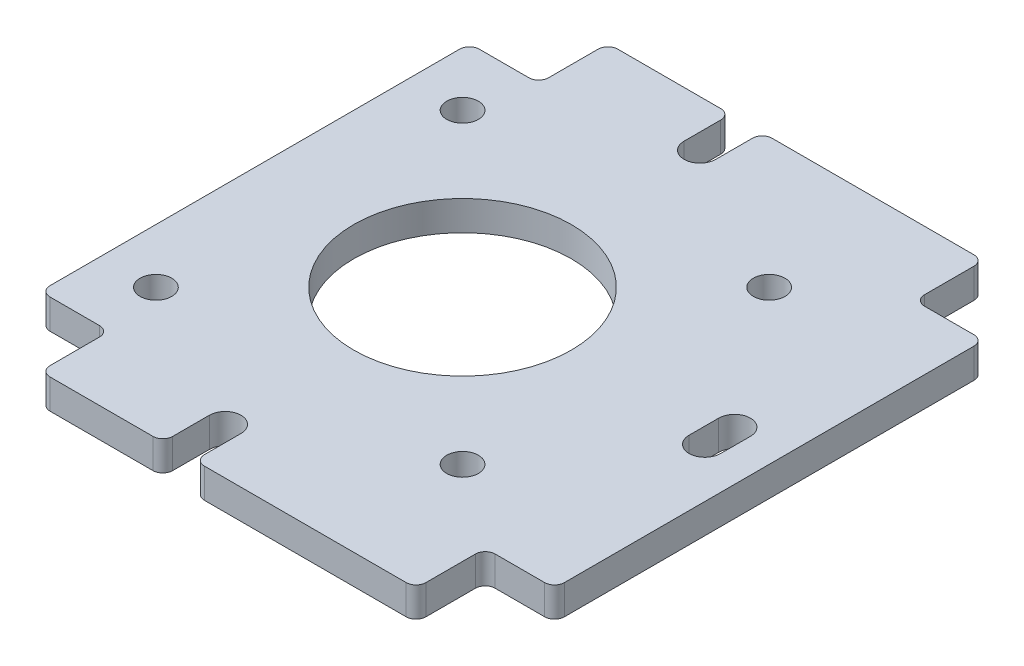
SolidWorks part; units mm, degrees
material "AISI 1045 Steel, cold drawn"
ref_plane "Front Plane" through (0, 0, 0) normal (0, 0, 1) x (1, 0, 0)
ref_plane "Top Plane" through (0, 0, 0) normal (0, 1, 0) x (1, 0, 0)
ref_plane "Right Plane" through (0, 0, 0) normal (1, 0, 0) x (0, 0, -1)
sketch "Sketch1" plane through (0, 0, 0) normal (0, 1, 0) x (1, 0, 0)
  line L1 (15.5, -15.5) -> (-15.5, -15.5) construction
  line L2 (15.5, -15.5) -> (15.5, 15.5) construction
  line L3 (15.5, 15.5) -> (-15.5, 15.5) construction
  line L4 (-15.5, -15.5) -> (-15.5, 15.5) construction
  line L5 (15.5, -15.5) -> (-15.5, 15.5) construction
  line L6 (15.5, 15.5) -> (-15.5, -15.5) construction
  line L7 (21, -21) -> (-21, -21)
  line L8 (21, -21) -> (21, 21)
  line L9 (21, 21) -> (-21, 21)
  line L10 (-21, -21) -> (-21, 21)
  line L11 (21, -21) -> (-21, 21) construction
  line L12 (21, 21) -> (-21, -21) construction
  circle A0 centre (0, 0) radius 11
  dimension "D1" = 22
  dimension "D2" = 31
  dimension "D3" = 42
extrude "Boss-Extrude1" add sketch "Sketch1" along normal mid plane 3
hole_wizard "M3 Clearance Hole1" positions "Sketch2" profile "Sketch3" hole size "M3" standard "ANSI Metric" end condition through all
sketch "Sketch2" plane through (0, 1.5, 0) normal (0, 1, 0) x (1, 0, 0)
  point P0 (-15.5, 15.5)
  point P3 (15.5, 15.5)
  point P6 (15.5, -15.5)
  point P9 (-15.5, -15.5)
sketch "Sketch3" plane through (-15.5, 1.5, -15.5) normal (1, 0, 0) x (0, 0, 1)
  line L0 (0, 0) -> (0, 3)
  line L1 (0, 3) -> (1.6, 3)
  line L2 (1.6, 3) -> (1.6, 0)
  line L5 (1.6, 0) -> (0, 0)
  line L11 (0, -6.35) -> (0, 107.95) construction
  dimension "Thru Hole Dia." = 3.2
  dimension "Thru Hole Depth" = 3
sketch "Sketch4" plane through (0, 1.5, 0) normal (0, 1, 0) x (1, 0, 0)
  line L0 (0, -24) -> (0, -29) construction
  line L1 (1.6, -24) -> (1.6, -28.7)
  line L2 (-1.6, -24) -> (-1.6, -28.7)
  line L3 (26, 1.5) -> (26, -1.5) construction
  line L4 (27.6, 1.5) -> (27.6, -1.5)
  line L5 (24.4, 1.5) -> (24.4, -1.5)
  line L6 (-14, -21) -> (14, -21)
  line L9 (-21, -21) -> (21, -21) construction
  line L11 (21, -21) -> (21, 21) construction
  line L12 (21, 0) -> (-21, 0) construction
  line L13 (0, 24) -> (0, 29) construction
  line L14 (1.6, 28.7) -> (14, 28.7)
  line L15 (-14, -21) -> (-14, -28.7)
  line L16 (-14, -28.7) -> (-1.6, -28.7)
  line L17 (14, -28.7) -> (14, -21)
  line L18 (-21, 21) -> (-21, -21) construction
  line L19 (1.6, -28.7) -> (14, -28.7)
  line L20 (14, 28.7) -> (14, 21)
  line L21 (-14, 28.7) -> (-1.6, 28.7)
  line L22 (-14, 21) -> (-14, 28.7)
  line L23 (-14, 21) -> (14, 21)
  line L24 (-1.6, 24) -> (-1.6, 28.7)
  line L25 (1.6, 24) -> (1.6, 28.7)
  line L26 (21, 14) -> (31, 14)
  line L27 (31, 14) -> (31, -14)
  line L28 (31, -14) -> (21, -14)
  line L29 (21, 21) -> (-21, 21) construction
  line L30 (21, 14) -> (21, -14)
  arc A0 (1.6, -24) -> (-1.6, -24) centre (0, -24) ccw
  arc A2 (27.6, 1.5) -> (24.4, 1.5) centre (26, 1.5) ccw
  arc A3 (24.4, -1.5) -> (27.6, -1.5) centre (26, -1.5) ccw
  arc A6 (1.6, 24) -> (-1.6, 24) centre (0, 24) cw
  point P10 (26, 0)
  point P17 (0, 0)
  dimension "D1" = 1.6
  dimension "D12" = 1.6
  dimension "D2" = 3
  dimension "D3" = 5
  dimension "D4" = 10
  dimension "D5" = 5
  dimension "D6" = 7.7
  dimension "D7" = 7
  dimension "D8" = 7
  dimension "D9" = 7
  dimension "D10" = 7
  dimension "D11" = 3
extrude "Boss-Extrude2" add sketch "Sketch4" against normal up to vertex (3 mm away) up to point (21, -1.5, -21)
sketch "Sketch5" plane through (0, 1.5, 0) normal (0, 1, 0) x (1, 0, 0)
  line L0 (21, -14) -> (31, -14) construction
  line L17 (31, 14) -> (21, 14)
  line L18 (31, 14) -> (31, 21)
  line L19 (31, 21) -> (21, 21)
  line L20 (21, 14) -> (21, 21)
  line L21 (14, 28.7) -> (24, 28.7)
  line L22 (14, 28.7) -> (14, 21)
  line L23 (14, 21) -> (24, 21)
  line L24 (24, 28.7) -> (24, 21)
  line L25 (31, -14) -> (21, -14)
  line L26 (31, -14) -> (31, -21)
  line L27 (31, -21) -> (21, -21)
  line L28 (21, -14) -> (21, -21)
  line L29 (31, -14) -> (31, 14) construction
  line L30 (-14, -21) -> (-14, -28.7) construction
  line L31 (14, -28.7) -> (24, -28.7)
  line L32 (14, -28.7) -> (14, -21)
  line L33 (14, -21) -> (24, -21)
  line L34 (24, -28.7) -> (24, -21)
  line L35 (-21, -21) -> (-14, -21)
  line L36 (-21, -21) -> (-21, -21.7)
  line L37 (-21, -21.7) -> (-14, -21.7)
  line L38 (-14, -21) -> (-14, -21.7)
  line L39 (-14, 28.7) -> (-14, 21) construction
  line L40 (-21, 21) -> (-14, 21)
  line L41 (-21, 21) -> (-21, 21.7)
  line L42 (-21, 21.7) -> (-14, 21.7)
  line L43 (-14, 21) -> (-14, 21.7)
  line L44 (-1.6, 28.7) -> (-14, 28.7) construction
  line L45 (31, 21) -> (24, 21)
  line L46 (31, 21) -> (31, 21.7)
  line L47 (31, 21.7) -> (24, 21.7)
  line L48 (24, 21) -> (24, 21.7)
  line L49 (31, -21) -> (24, -21)
  line L50 (31, -21) -> (31, -21.7)
  line L51 (31, -21.7) -> (24, -21.7)
  line L52 (24, -21) -> (24, -21.7)
  line L53 (-14, -28.7) -> (-1.6, -28.7) construction
  circle M1 centre (-15.5, 15.5) radius 1.6
  circle M2 centre (15.5, 15.5) radius 1.6
  circle M3 centre (15.5, -15.5) radius 1.6
  circle M4 centre (-15.5, -15.5) radius 1.6
  line M5 (-21, 21) -> (-21, -21)
  line M6 (-21, -21) -> (-14, -21)
  line M7 (-14, -21) -> (-14, -28.7)
  line M8 (-14, -28.7) -> (-1.6, -28.7)
  line M9 (-1.6, -28.7) -> (-1.6, -24)
  arc M10 (-1.6, -24) -> (1.6, -24) centre (0, -24) cw
  line M11 (1.6, -24) -> (1.6, -28.7)
  line M12 (1.6, -28.7) -> (14, -28.7)
  line M13 (14, -28.7) -> (14, -21)
  line M14 (14, -21) -> (21, -21)
  line M15 (21, -21) -> (21, -14)
  line M16 (21, -14) -> (31, -14)
  line M17 (31, -14) -> (31, 14)
  line M18 (31, 14) -> (21, 14)
  line M19 (21, 14) -> (21, 21)
  line M20 (21, 21) -> (14, 21)
  line M21 (14, 21) -> (14, 28.7)
  line M22 (14, 28.7) -> (1.6, 28.7)
  line M23 (1.6, 28.7) -> (1.6, 24)
  arc M24 (1.6, 24) -> (-1.6, 24) centre (0, 24) cw
  line M25 (-1.6, 24) -> (-1.6, 28.7)
  line M26 (-1.6, 28.7) -> (-14, 28.7)
  line M27 (-14, 28.7) -> (-14, 21)
  line M28 (-14, 21) -> (-21, 21)
  circle M29 centre (0, 0) radius 11
  line M30 (24.4, -1.5) -> (24.4, 1.5)
  arc M31 (24.4, 1.5) -> (27.6, 1.5) centre (26, 1.5) cw
  line M32 (27.6, 1.5) -> (27.6, -1.5)
  arc M33 (27.6, -1.5) -> (24.4, -1.5) centre (26, -1.5) cw
  dimension "D1" = 7
  dimension "D2" = 7
  dimension "D3" = 7
extrude "Boss-Extrude3" add sketch "Sketch5" against normal up to surface (3 mm away) contours M28 M5 M6 M7 M8 M9 M10 M11 M12 M13 M14 M15 M16 M17 M18 M19 M20 M21 M22 M23 M24 M25 M26 M27 M2 M4 M29 M33 M30 M31 M32 M3 M1 | M21 M20 | M19 M18 | L22 M16 M15 | L17 L20 M14 M13 | L36 L37 M7 M6 | L51 L50 L27 L34 | L46 L47 L24 L19 | L42 L41 M28 M27 region at (30.2255, 1.5, 0) region at (26, 1.5, -17.5) region at (27.5, 1.5, -21.35) region at (26, 1.5, 17.5) region at (19, 1.5, -24.85) region at (27.5, 1.5, 21.35) region at (19, 1.5, 24.85) region at (-17.5, 1.5, -21.35) region at (-17.5, 1.5, 21.35) up to face at (-15.5, -1.5, -13.9)
fillet "Fillet1" radius 1 16 edges at (-1.6, 0, 28.7) (1.6, 0, 28.7) (-14, 0, 28.7) (1.6, 0, -28.7) (-1.6, 0, -28.7) (-14, 0, -28.7) (24, 0, -28.7) (24, 0, 28.7) (-21, 0, 21.7) (-14, 0, 21.7) (24, 0, 21.7) (31, 0, 21.7) (31, 0, -21.7) (24, 0, -21.7) (-14, 0, -21.7) (-21, 0, -21.7)
